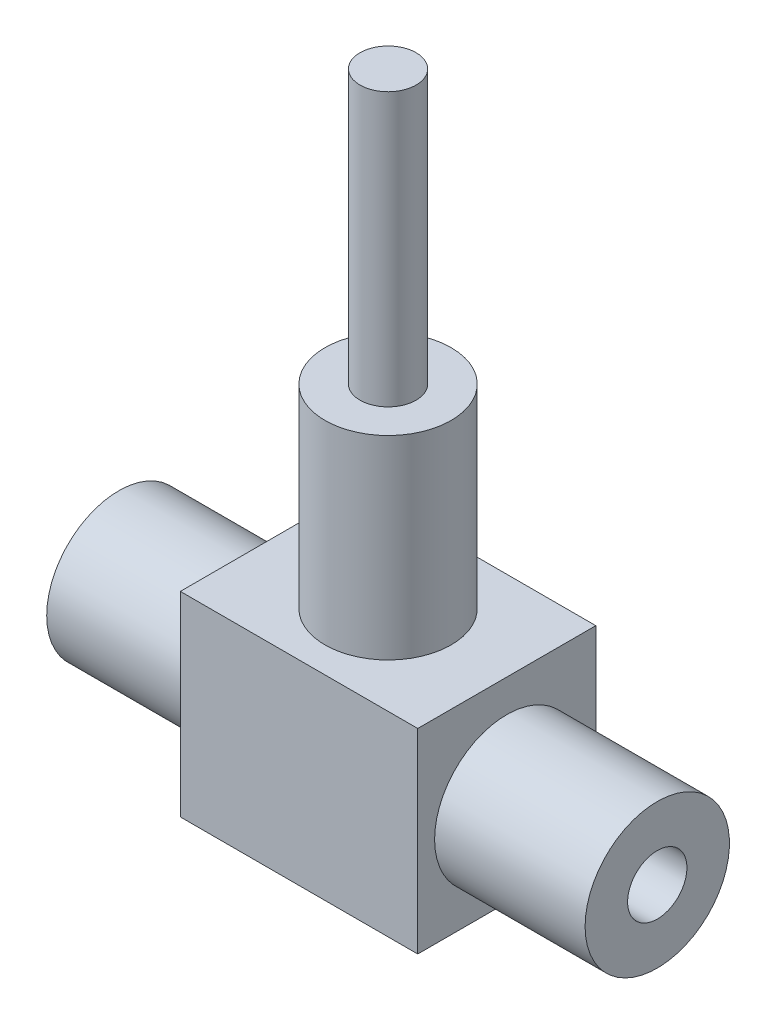
SolidWorks part; units mm, degrees
ref_plane "Front Plane" through (0, 0, 0) normal (0, 0, 1) x (1, 0, 0)
ref_plane "Top Plane" through (0, 0, 0) normal (0, 1, 0) x (1, 0, 0)
ref_plane "Right Plane" through (0, 0, 0) normal (1, 0, 0) x (0, 0, -1)
sketch "Body Sketch" plane through (0, 0, 0) normal (0, 0, 1) x (1, 0, 0)
  line L0 (-12.7, -9.7) -> (12.7, -9.7)
  line L1 (12.7, -9.7) -> (12.7, 11.2)
  line L2 (12.7, 11.2) -> (-12.7, 11.2)
  line L3 (-12.7, 11.2) -> (-12.7, -9.7)
extrude "Body" add sketch "Body Sketch" along normal mid plane 19.05
ref_axis "Engine Axis" through (31.68, 0, 0) along (-1, 0, 0)
ref_axis "Stem Axis" through (0, -13.245, 0) along (0, 1, 0)
sketch "Nut +X Sketch" plane through (0, 0, 0) normal (0, 0, 1) x (1, 0, 0)
  line L0 (-1000, 0) -> (1000, 0) construction
  line L1 (12.7, 0) -> (28.8, 0)
  line L2 (28.8, 0) -> (28.8, 7.722)
  line L3 (28.8, 7.722) -> (12.7, 7.722)
  line L4 (12.7, 7.722) -> (12.7, 0)
revolve "Nut +X" add sketch "Nut +X Sketch" angle 360 about L0
sketch "Nut -X Sketch" plane through (0, 0, 0) normal (0, 0, 1) x (1, 0, 0)
  line L0 (-1000, 0) -> (1000, 0) construction
  line L1 (-28.8, 0) -> (-12.7, 0)
  line L2 (-12.7, 0) -> (-12.7, 7.722)
  line L3 (-12.7, 7.722) -> (-28.8, 7.722)
  line L4 (-28.8, 7.722) -> (-28.8, 0)
revolve "Nut -X" add sketch "Nut -X Sketch" angle 360 about L0
sketch "Socket +X Sketch" plane through (0, 0, 0) normal (0, 0, 1) x (1, 0, 0)
  line L0 (-1000, 0) -> (1000, 0) construction
  line L1 (13.6, 0) -> (29.8, 0)
  line L2 (29.8, 0) -> (29.8, 3.175)
  line L3 (29.8, 3.175) -> (13.6, 3.175)
  line L4 (13.6, 3.175) -> (13.6, 0)
revolve "Socket +X" cut sketch "Socket +X Sketch" angle 360 about L0
sketch "Socket -X Sketch" plane through (0, 0, 0) normal (0, 0, 1) x (1, 0, 0)
  line L0 (-1000, 0) -> (1000, 0) construction
  line L1 (-29.8, 0) -> (-13.6, 0)
  line L2 (-13.6, 0) -> (-13.6, 3.175)
  line L3 (-13.6, 3.175) -> (-29.8, 3.175)
  line L4 (-29.8, 3.175) -> (-29.8, 0)
revolve "Socket -X" cut sketch "Socket -X Sketch" angle 360 about L0
sketch "Stem Sketch" plane through (0, 0, 0) normal (0, 0, 1) x (1, 0, 0)
  line L0 (0, -500) -> (0, 500) construction
  line L1 (0, 11.2) -> (6.75, 11.2)
  line L2 (6.75, 11.2) -> (6.75, 32)
  line L3 (6.75, 32) -> (3, 32)
  line L4 (3, 32) -> (3, 61.2)
  line L5 (3, 61.2) -> (0, 61.2)
  line L6 (0, 61.2) -> (0, 11.2)
revolve "Stem" add sketch "Stem Sketch" angle 360 about L0
